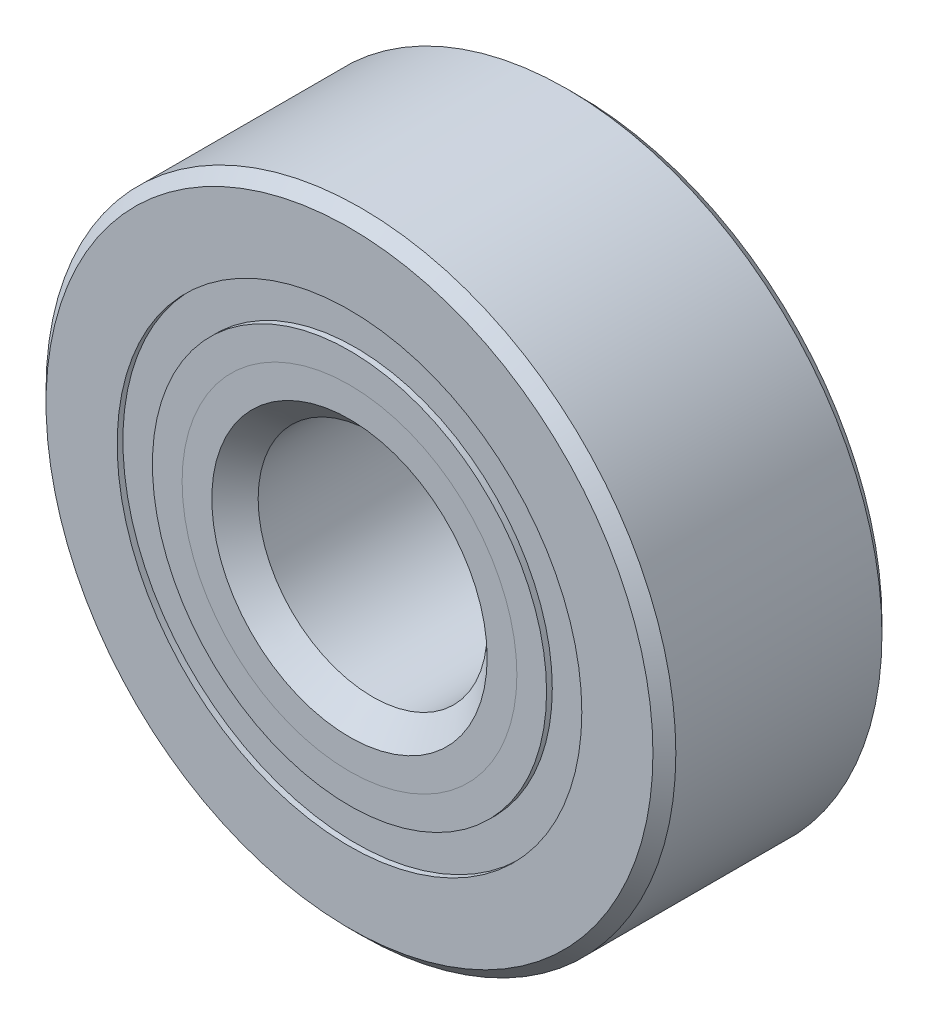
SolidWorks part; units mm, degrees
material "Cast Alloy Steel"
ref_plane "Front Plane" through (0, 0, 0) normal (0, 0, 1) x (1, 0, 0)
ref_plane "Top Plane" through (0, 0, 0) normal (0, 1, 0) x (1, 0, 0)
ref_plane "Right Plane" through (0, 0, 0) normal (1, 0, 0) x (0, 0, -1)
sketch "Sketch1" plane through (0, 0, 0) normal (1, 0, 0) x (0, 0, -1)
  line L0 (-3.175, 0) -> (3.175, 0) construction
  line L1 (0, 8.7312) -> (0, -8.7312) construction
  line L2 (2.8575, 8.7312) -> (-2.8575, 8.7312)
  line L3 (-2.8575, 8.7312) -> (-3.175, 8.4137)
  line L4 (-3.175, 8.4137) -> (-3.175, 6.4416)
  line L5 (-3.175, 6.4416) -> (-1.4111, 6.4416)
  line L6 (3.175, 6.4416) -> (1.4111, 6.4416)
  line L7 (3.175, 8.4137) -> (3.175, 6.4416)
  line L8 (2.8575, 8.7312) -> (3.175, 8.4137)
  line L9 (0, 8.7312) -> (0, 5.9531) construction
  line L10 (0, 5.9531) -> (0, 3.175) construction
  arc A0 (-1.4111, 6.4416) -> (1.4111, 6.4416) centre (0, 5.9531) cw
  point P14 (0, 3.175)
  dimension "D3" = 2.8222
  dimension "D1" = 45
  dimension "Width" = 6.35
  dimension "OD" = 17.4625
  dimension "D2" = 0.3175
  dimension "Shaft Dia" = 6.35
  dimension "D4" = 0.4885
revolve "Revolve1" add sketch "Sketch1" angle 360 about L0
sketch "Sketch2" plane through (0, 0, 0) normal (1, 0, 0) x (0, 0, -1)
  line L0 (-3.175, 5.4647) -> (-1.4111, 5.4647)
  line L1 (-3.175, 8.4137) -> (-3.175, -8.4137) construction
  line L2 (-3.175, 5.4647) -> (-3.175, 4.641)
  line L3 (-3.175, 4.641) -> (-2.3514, 3.8174)
  line L4 (-2.3514, 3.8174) -> (0, 3.8174)
  line L5 (0, 8.7312) -> (0, -8.7312) construction
  line L6 (0, 3.8174) -> (0, 4.4599)
  line L7 (0, 4.4599) -> (0, 3.175) construction
  line L8 (-3.175, 5.4647) -> (-3.175, 3.8174) construction
  line L9 (-3.175, 3.8174) -> (-2.3514, 3.8174) construction
  arc A0 (-1.4111, 5.4647) -> (0, 4.4599) centre (0, 5.9531) ccw
  arc A1 (1.4111, 6.4416) -> (-1.4111, 6.4416) centre (0, 5.9531) ccw construction
  circle A2 centre (0, 5.9531) radius 1.4933 construction
  dimension "D1" = 45
revolve "Revolve2" add sketch "Sketch2" angle 360 about L0
sketch "Sketch3" plane through (0, 0, 0) normal (1, 0, 0) x (0, 0, -1)
  line L0 (-3.175, 4.641) -> (-2.3514, 3.8174)
  line L1 (-2.3514, 3.8174) -> (0, 3.8174)
  line L2 (0, 3.8174) -> (0, 4.4599)
  line L3 (-3.175, 4.641) -> (-3.175, 3.8174)
  line L4 (-3.175, 5.4647) -> (-3.175, 3.8174) construction
  line L5 (-3.175, 3.8174) -> (-2.5326, 3.175)
  line L6 (-2.5326, 3.175) -> (2.8575, 3.175)
  line L7 (2.8575, 8.7312) -> (2.8575, -8.7312) construction
  line L8 (2.8575, 3.175) -> (3.175, 3.4925)
  line L9 (3.175, -8.4137) -> (3.175, 8.4137) construction
  line L10 (3.175, 3.4925) -> (3.175, 5.4647)
  line L11 (3.175, 5.4647) -> (1.4111, 5.4647)
  line L13 (2.8575, 8.7312) -> (3.175, 8.4137) construction
  circle A0 centre (0, 5.9531) radius 1.4933 construction
  arc A1 (1.4111, 5.4647) -> (0, 4.4599) centre (0, 5.9531) cw
revolve "Revolve3" add sketch "Sketch3" angle 360 about L0
sketch "Sketch4" plane through (0, 0, 0) normal (1, 0, 0) x (0, 0, -1)
  line L0 (-1.4933, 5.9531) -> (1.4933, 5.9531)
  circle A1 centre (0, 5.9531) radius 1.4933 construction
  arc A2 (-1.4933, 5.9531) -> (1.4933, 5.9531) centre (0, 5.9531) cw
  arc A3 (1.4111, 6.4416) -> (-1.4111, 6.4416) centre (0, 5.9531) ccw construction
revolve "Revolve4" add sketch "Sketch4" angle 360 about L0
ref_axis "Axis1" through (0, 0, -3.175) along (0, 0, 1)
pattern_circular "CirPattern1" count 8 every 45 about axis through (0, 0, -3.175) along (0, 0, 1) of bodies 104
sketch "Sketch5" plane through (0, 0, 0) normal (1, 0, 0) x (0, 0, -1)
  line L0 (-3.175, 6.4416) -> (-1.4111, 6.4416) construction
  line L1 (-3.0163, 6.4416) -> (-1.4933, 6.4416)
  line L2 (-3.0163, 6.4416) -> (-3.0163, 5.4647)
  line L3 (-3.0163, 5.4647) -> (-1.4933, 5.4647)
  line L4 (-1.4933, 6.4416) -> (-1.4933, 5.4647)
  line L5 (-3.175, 5.4647) -> (-1.4111, 5.4647) construction
  line L6 (-2.8575, 8.7312) -> (-3.175, 8.4137) construction
  line L7 (0, 8.7312) -> (0, 3.175) construction
  line L8 (3.0163, 5.4647) -> (1.4933, 5.4647)
  line L9 (1.4933, 6.4416) -> (1.4933, 5.4647)
  line L10 (3.0163, 6.4416) -> (1.4933, 6.4416)
  line L11 (3.0163, 6.4416) -> (3.0163, 5.4647)
  circle A0 centre (0, 5.9531) radius 1.4933 construction
  point P10 (-3.0163, 8.5725)
revolve "Revolve5" add sketch "Sketch5" angle 360 about L0
equation "\"D2@Sketch1\" = \"Width@Sketch1\"*.05"
equation "\"D3@Sketch1\" = \"Width@Sketch1\"/2.25"
equation "\"D4@Sketch1\" = (((\"OD@Sketch1\"-\"Width@Sketch1\")/2)/3.25)/3.5"
equation "\"D2@CirPattern1\" = 360/\"Balls@CirPattern1\""
